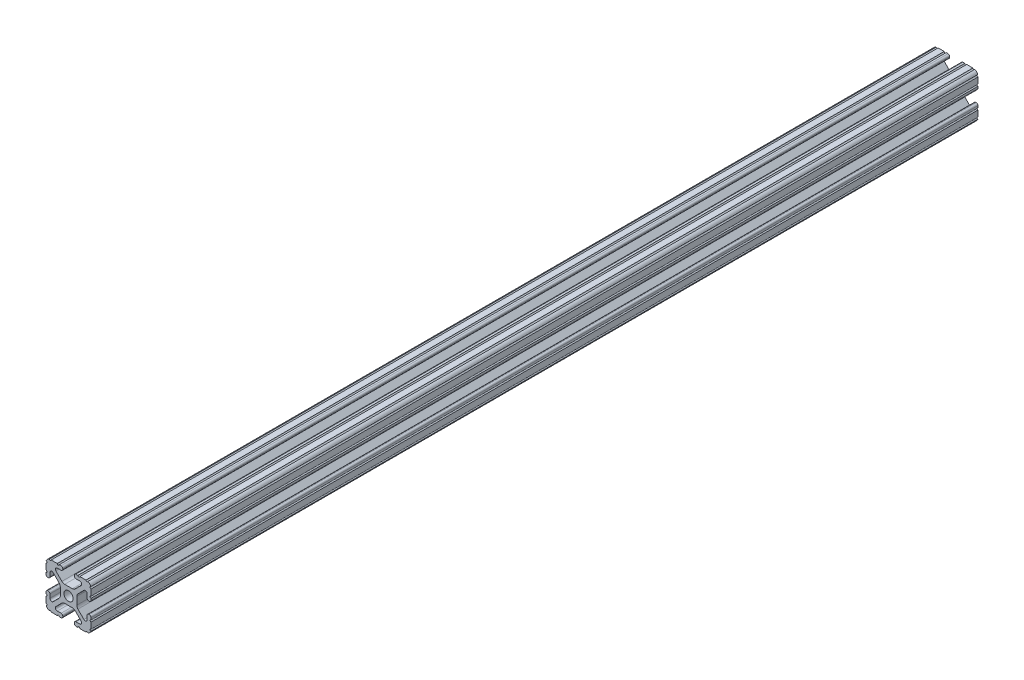
SolidWorks part; units mm, degrees
ref_plane "Front Plane" through (0, 0, 0) normal (0, 0, 1) x (1, 0, 0)
ref_plane "Top Plane" through (0, 0, 0) normal (0, 1, 0) x (1, 0, 0)
ref_plane "Right Plane" through (0, 0, 0) normal (1, 0, 0) x (0, 0, -1)
sketch "Sketch2" plane through (0, 0, 0) normal (0, 0, 1) x (1, 0, 0)
  line L0 (0, 12.7) -> (0, -12.7) construction
  line L1 (-12.7, 0) -> (12.7, 0) construction
  line L2 (3.2512, -12.7) -> (12.7, -12.7)
  line L3 (12.7, -12.7) -> (12.7, -3.2512)
  line L4 (3.2512, -12.7) -> (3.2512, -10.4902)
  line L5 (3.2512, -10.4902) -> (8.9276, -10.4902)
  line L6 (8.9276, -10.4902) -> (3.0856, -4.6482)
  line L7 (0, 0) -> (12.7, -12.7) construction
  line L8 (12.7, -3.2512) -> (10.4902, -3.2512)
  line L9 (10.4902, -3.2512) -> (10.4902, -8.9276)
  line L10 (10.4902, -8.9276) -> (4.6482, -3.0856)
  circle A0 centre (0, 0) radius 2.6035
  arc A1 (6.3485, -10.4902) -> (7.1039, -8.6665) centre (6.3485, -9.4219) ccw construction
  point P8 (0, -4.6482)
  dimension "Center Hole Diameter" = 5.207
  dimension "Rail Height" = 25.4
  dimension "Rail Width" = 25.4
  dimension "T-Slot Width" = 6.5024
  dimension "Slot Inner Width" = 14.8336
  dimension "Thickness" = 2.2098
  dimension "Slot Depth" = 5.842
  dimension "D1" = 2.2098
sketch "Sketch3" plane through (0, 0, 0) normal (1, 0, 0) x (0, 0, -1)
  line L0 (-76.2, -12.7) -> (76.2, -12.7) construction
  line L1 (-68.58, 0) -> (68.58, 0) construction
  dimension "Length" = 152.4
  dimension "D1" = 137.16
sketch "Sketch4" plane through (0, 0, 0) normal (0, 0, 1) x (1, 0, 0)
  line L0 (4.1904, -12.7) -> (10.1173, -12.7)
  line L1 (3.2512, -12.7) -> (12.7, -12.7) construction
  line L2 (3.2512, -12.7) -> (3.2512, -10.4902) construction
  line L3 (3.2512, -10.4902) -> (8.9276, -10.4902) construction
  line L4 (3.2512, -11.4294) -> (3.2512, -11.7608)
  line L5 (4.1904, -10.4902) -> (6.3485, -10.4902)
  line L6 (0, -4.6482) -> (2.164, -4.6482)
  line L7 (8.9276, -10.4902) -> (3.0856, -4.6482) construction
  line L8 (3.7373, -5.2999) -> (7.1039, -8.6665)
  line L9 (12.7, -12.7) -> (12.7, -3.2512) construction
  line L10 (10.4902, -8.9276) -> (4.6482, -3.0856) construction
  line L11 (10.4902, -3.2512) -> (10.4902, -8.9276) construction
  line L12 (10.4902, -6.3485) -> (10.4902, -4.1904)
  line L13 (12.7, -3.2512) -> (10.4902, -3.2512) construction
  line L14 (11.4294, -3.2512) -> (11.7608, -3.2512)
  line L15 (12.7, -4.1904) -> (12.7, -10.1173)
  line L16 (8.6665, -7.1039) -> (5.2999, -3.7373)
  line L17 (4.6482, 0) -> (4.6482, -2.164)
  line L18 (-12.7, 0) -> (12.7, 0) construction
  line L19 (0, -4.6482) -> (0, -2.6035)
  line L20 (0, 12.7) -> (0, -12.7) construction
  line L21 (4.6482, 0) -> (2.6035, 0)
  arc A0 (3.2512, -11.7608) -> (4.1904, -12.7) centre (4.1904, -11.7608) ccw
  arc A2 (3.2512, -11.4294) -> (4.1904, -10.4902) centre (4.1904, -11.4294) cw
  arc A3 (6.3485, -10.4902) -> (7.1039, -8.6665) centre (6.3485, -9.4219) ccw
  arc A4 (2.164, -4.6482) -> (3.7373, -5.2999) centre (2.164, -6.8732) cw
  arc A5 (10.1173, -12.7) -> (12.7, -10.1173) centre (10.1173, -10.1173) ccw
  arc A6 (8.6665, -7.1039) -> (10.4902, -6.3485) centre (9.4219, -6.3485) ccw
  arc A7 (10.4902, -4.1904) -> (11.4294, -3.2512) centre (11.4294, -4.1904) cw
  arc A8 (11.7608, -3.2512) -> (12.7, -4.1904) centre (11.7608, -4.1904) cw
  arc A9 (5.2999, -3.7373) -> (4.6482, -2.164) centre (6.8732, -2.164) cw
  circle A10 centre (0, 0) radius 2.6035 construction
  arc A11 (0, -2.6035) -> (2.6035, 0) centre (0, 0) ccw
  dimension "D1" = 2.5827
  dimension "D2" = 2.225
  dimension "D3" = 0.9392
extrude "Boss-Extrude1" add sketch "Sketch4" along normal mid plane 152.4
sketch "Sketch5" plane through (0, 0, 0) normal (0, 0, 1) x (1, 0, 0)
  line L0 (3.2512, -12.7) -> (12.7, -12.7) construction
  line L1 (4.1904, -10.4902) -> (6.3485, -10.4902) construction
  line L3 (0, 0) -> (12.7, -12.7) construction
  line L4 (6.3485, -10.4902) -> (6.3485, -12.7) construction
  line L5 (8.9276, -10.4902) -> (3.0856, -4.6482) construction
  circle A0 centre (10.3562, -12.7) radius 0.5524
  circle A1 centre (5.796, -12.7) radius 0.5524
  circle A2 centre (12.7, -10.3562) radius 0.5524
  circle A3 centre (12.7, -5.796) radius 0.5524
  point P10 (5.2694, -10.4902)
  point P12 (9.4219, -6.3485)
  dimension "D1" = 1.1049
extrude "Cut-Extrude1" cut sketch "Sketch5" against normal through all both and the other way through all
mirror "Mirror1" about plane through (0, 0, 0) normal (1, 0, 0) of bodies 137 134
mirror "Mirror2" about plane through (0, 0, 0) normal (0, 1, 0) of bodies 135
sketch "Sketch6" plane through (0, 0, 76.2) normal (0, 0, 1) x (1, 0, 0)
  line L44 (12.7, -5.2436) -> (12.7, -4.1904)
  line L45 (11.7608, -3.2512) -> (11.4294, -3.2512)
  line L46 (10.4902, -4.1904) -> (10.4902, -6.3485)
  line L47 (8.6665, -7.1039) -> (5.2999, -3.7373)
  line L48 (4.6482, -2.164) -> (4.6482, 2.164)
  line L49 (5.2999, 3.7373) -> (8.6665, 7.1039)
  line L50 (10.4902, 6.3485) -> (10.4902, 4.1904)
  line L51 (11.4294, 3.2512) -> (11.7608, 3.2512)
  line L52 (12.7, 4.1904) -> (12.7, 5.2436)
  line L53 (12.7, 6.3485) -> (12.7, 9.8037)
  line L54 (9.8037, 12.7) -> (6.3485, 12.7)
  line L55 (5.2436, 12.7) -> (4.1904, 12.7)
  line L56 (3.2512, 11.7608) -> (3.2512, 11.4294)
  line L57 (4.1904, 10.4902) -> (6.3485, 10.4902)
  line L58 (7.1039, 8.6665) -> (3.7373, 5.2999)
  line L59 (2.164, 4.6482) -> (-2.164, 4.6482)
  line L60 (-3.7373, 5.2999) -> (-7.1039, 8.6665)
  line L61 (-6.3485, 10.4902) -> (-4.1904, 10.4902)
  line L62 (-3.2512, 11.4294) -> (-3.2512, 11.7608)
  line L63 (-4.1904, 12.7) -> (-5.2436, 12.7)
  line L64 (-6.3485, 12.7) -> (-9.8037, 12.7)
  line L65 (-12.7, 9.8037) -> (-12.7, 6.3485)
  line L66 (-12.7, 5.2436) -> (-12.7, 4.1904)
  line L67 (-11.7608, 3.2512) -> (-11.4294, 3.2512)
  line L68 (-10.4902, 4.1904) -> (-10.4902, 6.3485)
  line L69 (-8.6665, 7.1039) -> (-5.2999, 3.7373)
  line L70 (-4.6482, 2.164) -> (-4.6482, -2.164)
  line L71 (-5.2999, -3.7373) -> (-8.6665, -7.1039)
  line L72 (-10.4902, -6.3485) -> (-10.4902, -4.1904)
  line L73 (-11.4294, -3.2512) -> (-11.7608, -3.2512)
  line L74 (-12.7, -4.1904) -> (-12.7, -5.2436)
  line L75 (-12.7, -6.3485) -> (-12.7, -9.8037)
  line L76 (-9.8037, -12.7) -> (-6.3485, -12.7)
  line L77 (-5.2436, -12.7) -> (-4.1904, -12.7)
  line L78 (-3.2512, -11.7608) -> (-3.2512, -11.4294)
  line L79 (-4.1904, -10.4902) -> (-6.3485, -10.4902)
  line L80 (-7.1039, -8.6665) -> (-3.7373, -5.2999)
  line L81 (-2.164, -4.6482) -> (2.164, -4.6482)
  line L82 (3.7373, -5.2999) -> (7.1039, -8.6665)
  line L83 (6.3485, -10.4902) -> (4.1904, -10.4902)
  line L84 (3.2512, -11.4294) -> (3.2512, -11.7608)
  line L85 (4.1904, -12.7) -> (5.2436, -12.7)
  line L86 (6.3485, -12.7) -> (9.8037, -12.7)
  line L87 (12.7, -9.8037) -> (12.7, -6.3485)
  line L88 (12.7, -5.2436) -> (12.7, -4.1904)
  line L89 (11.7608, -3.2512) -> (11.4294, -3.2512)
  line L90 (10.4902, -4.1904) -> (10.4902, -6.3485)
  line L91 (8.6665, -7.1039) -> (5.2999, -3.7373)
  line L92 (4.6482, -2.164) -> (4.6482, 2.164)
  line L93 (5.2999, 3.7373) -> (8.6665, 7.1039)
  line L94 (10.4902, 6.3485) -> (10.4902, 4.1904)
  line L95 (11.4294, 3.2512) -> (11.7608, 3.2512)
  line L96 (12.7, 4.1904) -> (12.7, 5.2436)
  line L97 (12.7, 6.3485) -> (12.7, 9.8037)
  line L98 (9.8037, 12.7) -> (6.3485, 12.7)
  line L99 (5.2436, 12.7) -> (4.1904, 12.7)
  line L100 (3.2512, 11.7608) -> (3.2512, 11.4294)
  line L101 (4.1904, 10.4902) -> (6.3485, 10.4902)
  line L102 (7.1039, 8.6665) -> (3.7373, 5.2999)
  line L103 (2.164, 4.6482) -> (-2.164, 4.6482)
  line L104 (-3.7373, 5.2999) -> (-7.1039, 8.6665)
  line L105 (-6.3485, 10.4902) -> (-4.1904, 10.4902)
  line L106 (-3.2512, 11.4294) -> (-3.2512, 11.7608)
  line L107 (-4.1904, 12.7) -> (-5.2436, 12.7)
  line L108 (-6.3485, 12.7) -> (-9.8037, 12.7)
  line L109 (-12.7, 9.8037) -> (-12.7, 6.3485)
  line L110 (-12.7, 5.2436) -> (-12.7, 4.1904)
  line L111 (-11.7608, 3.2512) -> (-11.4294, 3.2512)
  line L112 (-10.4902, 4.1904) -> (-10.4902, 6.3485)
  line L113 (-8.6665, 7.1039) -> (-5.2999, 3.7373)
  line L114 (-4.6482, 2.164) -> (-4.6482, -2.164)
  line L115 (-5.2999, -3.7373) -> (-8.6665, -7.1039)
  line L116 (-10.4902, -6.3485) -> (-10.4902, -4.1904)
  line L117 (-11.4294, -3.2512) -> (-11.7608, -3.2512)
  line L118 (-12.7, -4.1904) -> (-12.7, -5.2436)
  line L119 (-12.7, -6.3485) -> (-12.7, -9.8037)
  line L120 (-9.8037, -12.7) -> (-6.3485, -12.7)
  line L121 (-5.2436, -12.7) -> (-4.1904, -12.7)
  line L122 (-3.2512, -11.7608) -> (-3.2512, -11.4294)
  line L123 (-4.1904, -10.4902) -> (-6.3485, -10.4902)
  line L124 (-7.1039, -8.6665) -> (-3.7373, -5.2999)
  line L125 (-2.164, -4.6482) -> (2.164, -4.6482)
  line L126 (3.7373, -5.2999) -> (7.1039, -8.6665)
  line L127 (6.3485, -10.4902) -> (4.1904, -10.4902)
  line L128 (3.2512, -11.4294) -> (3.2512, -11.7608)
  line L129 (4.1904, -12.7) -> (5.2436, -12.7)
  line L130 (6.3485, -12.7) -> (9.8037, -12.7)
  line L131 (12.7, -9.8037) -> (12.7, -6.3485)
  circle A0 centre (0, 0) radius 2.6035
  arc A52 (12.7, -5.2436) -> (12.7, -6.3485) centre (12.7, -5.796) ccw
  arc A53 (12.7, -4.1904) -> (11.7608, -3.2512) centre (11.7608, -4.1904) ccw
  arc A54 (11.4294, -3.2512) -> (10.4902, -4.1904) centre (11.4294, -4.1904) ccw
  arc A55 (8.6665, -7.1039) -> (10.4902, -6.3485) centre (9.4219, -6.3485) ccw
  arc A56 (4.6482, -2.164) -> (5.2999, -3.7373) centre (6.8732, -2.164) ccw
  arc A57 (5.2999, 3.7373) -> (4.6482, 2.164) centre (6.8732, 2.164) ccw
  arc A58 (10.4902, 6.3485) -> (8.6665, 7.1039) centre (9.4219, 6.3485) ccw
  arc A59 (10.4902, 4.1904) -> (11.4294, 3.2512) centre (11.4294, 4.1904) ccw
  arc A60 (11.7608, 3.2512) -> (12.7, 4.1904) centre (11.7608, 4.1904) ccw
  arc A61 (12.7, 6.3485) -> (12.7, 5.2436) centre (12.7, 5.796) ccw
  arc A62 (12.58, 10.8954) -> (12.7, 9.8037) centre (12.7, 10.3562) ccw
  arc A63 (12.58, 10.8954) -> (10.8954, 12.58) centre (10.1173, 10.1173) ccw
  arc A64 (9.8037, 12.7) -> (10.8954, 12.58) centre (10.3562, 12.7) ccw
  arc A65 (5.2436, 12.7) -> (6.3485, 12.7) centre (5.796, 12.7) ccw
  arc A66 (4.1904, 12.7) -> (3.2512, 11.7608) centre (4.1904, 11.7608) ccw
  arc A67 (3.2512, 11.4294) -> (4.1904, 10.4902) centre (4.1904, 11.4294) ccw
  arc A68 (7.1039, 8.6665) -> (6.3485, 10.4902) centre (6.3485, 9.4219) ccw
  arc A69 (2.164, 4.6482) -> (3.7373, 5.2999) centre (2.164, 6.8732) ccw
  arc A70 (-3.7373, 5.2999) -> (-2.164, 4.6482) centre (-2.164, 6.8732) ccw
  arc A71 (-6.3485, 10.4902) -> (-7.1039, 8.6665) centre (-6.3485, 9.4219) ccw
  arc A72 (-4.1904, 10.4902) -> (-3.2512, 11.4294) centre (-4.1904, 11.4294) ccw
  arc A73 (-3.2512, 11.7608) -> (-4.1904, 12.7) centre (-4.1904, 11.7608) ccw
  arc A74 (-6.3485, 12.7) -> (-5.2436, 12.7) centre (-5.796, 12.7) ccw
  arc A75 (-10.8954, 12.58) -> (-9.8037, 12.7) centre (-10.3562, 12.7) ccw
  arc A76 (-10.8954, 12.58) -> (-12.58, 10.8954) centre (-10.1173, 10.1173) ccw
  arc A77 (-12.7, 9.8037) -> (-12.58, 10.8954) centre (-12.7, 10.3562) ccw
  arc A78 (-12.7, 5.2436) -> (-12.7, 6.3485) centre (-12.7, 5.796) ccw
  arc A79 (-12.7, 4.1904) -> (-11.7608, 3.2512) centre (-11.7608, 4.1904) ccw
  arc A80 (-11.4294, 3.2512) -> (-10.4902, 4.1904) centre (-11.4294, 4.1904) ccw
  arc A81 (-8.6665, 7.1039) -> (-10.4902, 6.3485) centre (-9.4219, 6.3485) ccw
  arc A82 (-4.6482, 2.164) -> (-5.2999, 3.7373) centre (-6.8732, 2.164) ccw
  arc A83 (-5.2999, -3.7373) -> (-4.6482, -2.164) centre (-6.8732, -2.164) ccw
  arc A84 (-10.4902, -6.3485) -> (-8.6665, -7.1039) centre (-9.4219, -6.3485) ccw
  arc A85 (-10.4902, -4.1904) -> (-11.4294, -3.2512) centre (-11.4294, -4.1904) ccw
  arc A86 (-11.7608, -3.2512) -> (-12.7, -4.1904) centre (-11.7608, -4.1904) ccw
  arc A87 (-12.7, -6.3485) -> (-12.7, -5.2436) centre (-12.7, -5.796) ccw
  arc A88 (-12.58, -10.8954) -> (-12.7, -9.8037) centre (-12.7, -10.3562) ccw
  arc A89 (-12.58, -10.8954) -> (-10.8954, -12.58) centre (-10.1173, -10.1173) ccw
  arc A90 (-9.8037, -12.7) -> (-10.8954, -12.58) centre (-10.3562, -12.7) ccw
  arc A91 (-5.2436, -12.7) -> (-6.3485, -12.7) centre (-5.796, -12.7) ccw
  arc A92 (-4.1904, -12.7) -> (-3.2512, -11.7608) centre (-4.1904, -11.7608) ccw
  arc A93 (-3.2512, -11.4294) -> (-4.1904, -10.4902) centre (-4.1904, -11.4294) ccw
  arc A94 (-7.1039, -8.6665) -> (-6.3485, -10.4902) centre (-6.3485, -9.4219) ccw
  arc A95 (-2.164, -4.6482) -> (-3.7373, -5.2999) centre (-2.164, -6.8732) ccw
  arc A96 (3.7373, -5.2999) -> (2.164, -4.6482) centre (2.164, -6.8732) ccw
  arc A97 (6.3485, -10.4902) -> (7.1039, -8.6665) centre (6.3485, -9.4219) ccw
  arc A98 (4.1904, -10.4902) -> (3.2512, -11.4294) centre (4.1904, -11.4294) ccw
  arc A99 (3.2512, -11.7608) -> (4.1904, -12.7) centre (4.1904, -11.7608) ccw
  arc A100 (6.3485, -12.7) -> (5.2436, -12.7) centre (5.796, -12.7) ccw
  arc A101 (10.8954, -12.58) -> (9.8037, -12.7) centre (10.3562, -12.7) ccw
  arc A102 (10.8954, -12.58) -> (12.58, -10.8954) centre (10.1173, -10.1173) ccw
  arc A103 (12.7, -9.8037) -> (12.58, -10.8954) centre (12.7, -10.3562) ccw
  arc A104 (12.7, -5.2436) -> (12.7, -6.3485) centre (12.7, -5.796) ccw
  arc A105 (12.7, -4.1904) -> (11.7608, -3.2512) centre (11.7608, -4.1904) ccw
  arc A106 (11.4294, -3.2512) -> (10.4902, -4.1904) centre (11.4294, -4.1904) ccw
  arc A107 (8.6665, -7.1039) -> (10.4902, -6.3485) centre (9.4219, -6.3485) ccw
  arc A108 (4.6482, -2.164) -> (5.2999, -3.7373) centre (6.8732, -2.164) ccw
  arc A109 (5.2999, 3.7373) -> (4.6482, 2.164) centre (6.8732, 2.164) ccw
  arc A110 (10.4902, 6.3485) -> (8.6665, 7.1039) centre (9.4219, 6.3485) ccw
  arc A111 (10.4902, 4.1904) -> (11.4294, 3.2512) centre (11.4294, 4.1904) ccw
  arc A112 (11.7608, 3.2512) -> (12.7, 4.1904) centre (11.7608, 4.1904) ccw
  arc A113 (12.7, 6.3485) -> (12.7, 5.2436) centre (12.7, 5.796) ccw
  arc A114 (12.58, 10.8954) -> (12.7, 9.8037) centre (12.7, 10.3562) ccw
  arc A115 (12.58, 10.8954) -> (10.8954, 12.58) centre (10.1173, 10.1173) ccw
  arc A116 (9.8037, 12.7) -> (10.8954, 12.58) centre (10.3562, 12.7) ccw
  arc A117 (5.2436, 12.7) -> (6.3485, 12.7) centre (5.796, 12.7) ccw
  arc A118 (4.1904, 12.7) -> (3.2512, 11.7608) centre (4.1904, 11.7608) ccw
  arc A119 (3.2512, 11.4294) -> (4.1904, 10.4902) centre (4.1904, 11.4294) ccw
  arc A120 (7.1039, 8.6665) -> (6.3485, 10.4902) centre (6.3485, 9.4219) ccw
  arc A121 (2.164, 4.6482) -> (3.7373, 5.2999) centre (2.164, 6.8732) ccw
  arc A122 (-3.7373, 5.2999) -> (-2.164, 4.6482) centre (-2.164, 6.8732) ccw
  arc A123 (-6.3485, 10.4902) -> (-7.1039, 8.6665) centre (-6.3485, 9.4219) ccw
  arc A124 (-4.1904, 10.4902) -> (-3.2512, 11.4294) centre (-4.1904, 11.4294) ccw
  arc A125 (-3.2512, 11.7608) -> (-4.1904, 12.7) centre (-4.1904, 11.7608) ccw
  arc A126 (-6.3485, 12.7) -> (-5.2436, 12.7) centre (-5.796, 12.7) ccw
  arc A127 (-10.8954, 12.58) -> (-9.8037, 12.7) centre (-10.3562, 12.7) ccw
  arc A128 (-10.8954, 12.58) -> (-12.58, 10.8954) centre (-10.1173, 10.1173) ccw
  arc A129 (-12.7, 9.8037) -> (-12.58, 10.8954) centre (-12.7, 10.3562) ccw
  arc A130 (-12.7, 5.2436) -> (-12.7, 6.3485) centre (-12.7, 5.796) ccw
  arc A131 (-12.7, 4.1904) -> (-11.7608, 3.2512) centre (-11.7608, 4.1904) ccw
  arc A132 (-11.4294, 3.2512) -> (-10.4902, 4.1904) centre (-11.4294, 4.1904) ccw
  arc A133 (-8.6665, 7.1039) -> (-10.4902, 6.3485) centre (-9.4219, 6.3485) ccw
  arc A134 (-4.6482, 2.164) -> (-5.2999, 3.7373) centre (-6.8732, 2.164) ccw
  arc A135 (-5.2999, -3.7373) -> (-4.6482, -2.164) centre (-6.8732, -2.164) ccw
  arc A136 (-10.4902, -6.3485) -> (-8.6665, -7.1039) centre (-9.4219, -6.3485) ccw
  arc A137 (-10.4902, -4.1904) -> (-11.4294, -3.2512) centre (-11.4294, -4.1904) ccw
  arc A138 (-11.7608, -3.2512) -> (-12.7, -4.1904) centre (-11.7608, -4.1904) ccw
  arc A139 (-12.7, -6.3485) -> (-12.7, -5.2436) centre (-12.7, -5.796) ccw
  arc A140 (-12.58, -10.8954) -> (-12.7, -9.8037) centre (-12.7, -10.3562) ccw
  arc A141 (-12.58, -10.8954) -> (-10.8954, -12.58) centre (-10.1173, -10.1173) ccw
  arc A142 (-9.8037, -12.7) -> (-10.8954, -12.58) centre (-10.3562, -12.7) ccw
  arc A143 (-5.2436, -12.7) -> (-6.3485, -12.7) centre (-5.796, -12.7) ccw
  arc A144 (-4.1904, -12.7) -> (-3.2512, -11.7608) centre (-4.1904, -11.7608) ccw
  arc A145 (-3.2512, -11.4294) -> (-4.1904, -10.4902) centre (-4.1904, -11.4294) ccw
  arc A146 (-7.1039, -8.6665) -> (-6.3485, -10.4902) centre (-6.3485, -9.4219) ccw
  arc A147 (-2.164, -4.6482) -> (-3.7373, -5.2999) centre (-2.164, -6.8732) ccw
  arc A148 (3.7373, -5.2999) -> (2.164, -4.6482) centre (2.164, -6.8732) ccw
  arc A149 (6.3485, -10.4902) -> (7.1039, -8.6665) centre (6.3485, -9.4219) ccw
  arc A150 (4.1904, -10.4902) -> (3.2512, -11.4294) centre (4.1904, -11.4294) ccw
  arc A151 (3.2512, -11.7608) -> (4.1904, -12.7) centre (4.1904, -11.7608) ccw
  arc A152 (6.3485, -12.7) -> (5.2436, -12.7) centre (5.796, -12.7) ccw
  arc A153 (10.8954, -12.58) -> (9.8037, -12.7) centre (10.3562, -12.7) ccw
  arc A154 (10.8954, -12.58) -> (12.58, -10.8954) centre (10.1173, -10.1173) ccw
  arc A155 (12.7, -9.8037) -> (12.58, -10.8954) centre (12.7, -10.3562) ccw
  dimension "D1" = 0
extrude "Boss-Extrude2" add sketch "Sketch6" along normal blind 347.6002
equation "\"D1@Boss-Extrude1\"=\"Length@Sketch3\""
equation "\"D1@Sketch2\"=\"Thickness@Sketch2\""
equation "\"D2@Sketch4\"=\"Slot Inner Width@Sketch2\"*0.15"
equation "\"D1@Sketch4\"=\"D3@Sketch4\"*2.75"
equation "\"D3@Sketch4\"=\"Thickness@Sketch2\"*0.425"
equation "\"D1@Sketch5\"=\"Thickness@Sketch2\"*0.5"
equation "\"D1@Sketch3\"=\"Length@Sketch3\"*0.9"
equation "\"D1@Boss-Extrude2\"=23.6-6-3.937+0.022047244"
